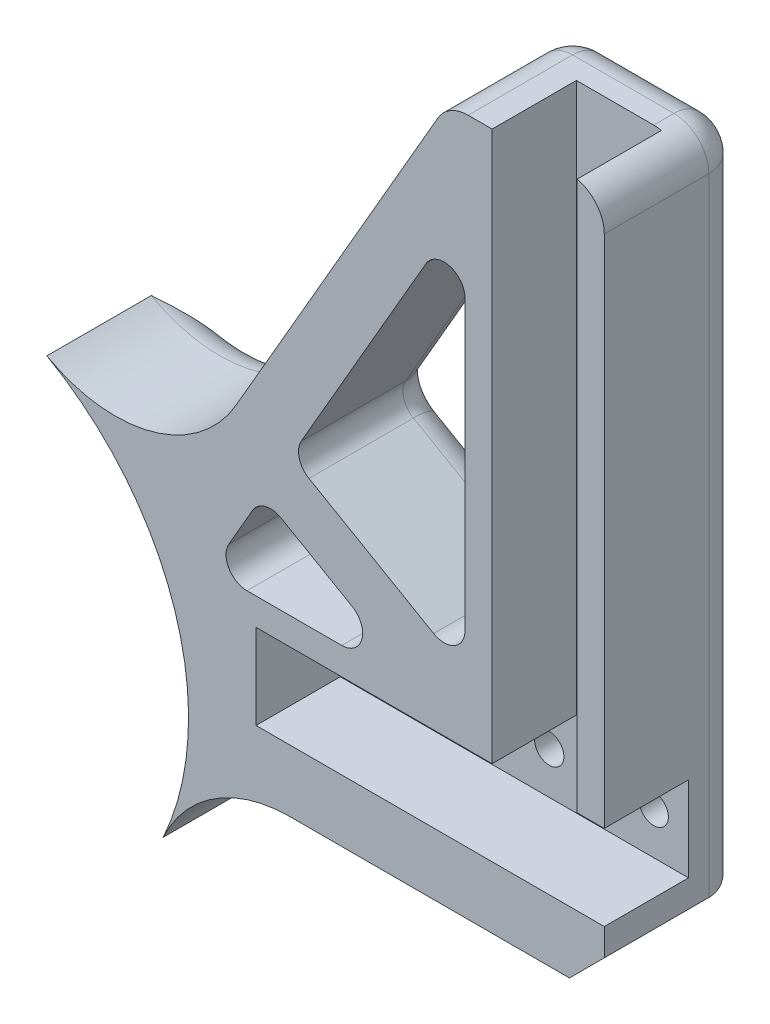
SolidWorks part; units mm, degrees
material "ABS"
ref_plane "前视基准面" through (0, 0, 0) normal (0, 0, 1) x (1, 0, 0)
ref_plane "上视基准面" through (0, 0, 0) normal (0, 1, 0) x (1, 0, 0)
ref_plane "右视基准面" through (0, 0, 0) normal (1, 0, 0) x (0, 0, -1)
other "Configuration Table"
sketch "草图1" plane through (0, 0, 0) normal (0, 0, 1) x (1, 0, 0)
  circle A0 centre (0, 0) radius 40
  circle A10 centre (0, 0) radius 32.5
  dimension "D1" = 80
  dimension "D6" = 65
extrude "凸台-拉伸1" add sketch "草图1" along normal blind 20
sketch "草图2" plane through (0, 0, 20) normal (0, 0, 1) x (1, 0, 0)
  line L0 (0, 0) -> (40, 0) construction
  line L1 (0, 0) -> (36.5, 0) construction
  circle A0 centre (0, 0) radius 40 construction
  point P6 (36.5, 0)
  point P7 (27.9606, -23.4617)
  point P10 (6.3382, -35.9455)
  point P11 (-18.25, -31.6099)
  point P12 (-34.2988, -12.4837)
  point P13 (-34.2988, 12.4837)
  point P14 (-18.25, 31.6099)
  point P15 (6.3382, 35.9455)
  point P16 (27.9606, 23.4617)
  dimension "D3" = 36.5
  dimension "D2" = 9
hole_wizard "M3 六角凹锥坑螺钉的锥形沉头孔1" [suppressed] positions "草图2" profile "草图3" countersink size "M3" standard "ISO"
sketch "草图3" plane through (27.9606, 23.4617, 4) normal (1, 0, 0) x (0, -1, 0)
  line L0 (0, 0) -> (0, 4)
  line L1 (0, 4) -> (1.7, 4)
  line L2 (1.7, 4) -> (1.7, 1.66)
  line L3 (1.7, 1.66) -> (3.36, 0)
  line L5 (3.36, 0) -> (0, 0)
  line L6 (-1.7, 1.66) -> (-3.36, 0) construction
  line L11 (0, -6.35) -> (0, 107.95) construction
  dimension "通孔孔直径" = 3.4
  dimension "通孔孔深度" = 4
  dimension "近端锥形沉头孔直径" = 6.72
  dimension "近端锥形沉头孔角度" = 90
sketch "草图4" plane through (0, 0, 20) normal (0, 0, 1) x (1, 0, 0)
  line L0 (0, 0) -> (40, 0) construction
  line L11 (39.6863, -5) -> (99.6863, -5)
  line L23 (77.2499, 95) -> (99.6863, 95)
  line L26 (99.6863, 95) -> (99.6863, -5)
  line L27 (77.2499, 95) -> (34.2914, 20.5937)
  line L28 (79.6863, 83.2199) -> (43.1863, 20) construction
  line L29 (43.1863, 20) -> (79.6863, 20) construction
  line L30 (79.6863, 20) -> (79.6863, 83.2199) construction
  line L32 (54.6863, 39.9186) -> (79.6863, 25.4848)
  line L33 (50.6863, 32.9904) -> (73.1863, 20)
  line L34 (79.6863, 83.2199) -> (54.6863, 39.9186)
  line L35 (79.6863, 83.2199) -> (79.6863, 25.4848)
  line L36 (50.6863, 32.9904) -> (43.1863, 20)
  line L37 (43.1863, 20) -> (73.1863, 20)
  line L38 (89.6863, 95) -> (89.6863, -5) construction
  circle A0 centre (0, 0) radius 40 construction
  circle A5 centre (79.6863, 10) radius 1.55
  circle A13 centre (94.6863, 10) radius 1.55
  circle A29 centre (64.6863, 10) radius 1.55
  circle A34 centre (89.6863, 76) radius 1.55
  arc A42 (34.2914, 20.5937) -> (39.6863, -5) centre (0, 0) cw
  circle A43 centre (89.6863, 61) radius 1.55
  circle A44 centre (89.6863, 46) radius 1.55
  circle A45 centre (89.6863, 31) radius 1.55
  dimension "D1" = 5
  dimension "D2" = 20
  dimension "D8" = 3.1
  dimension "D9" = 3.1
  dimension "D10" = 15
  dimension "D15" = 15
  dimension "D16" = 15
  dimension "D18" = 10
  dimension "D19" = 3.1
  dimension "D25" = 15
  dimension "D26" = 50
  dimension "D27" = 3.1
  dimension "D6" = 60
  dimension "D11" = 15
  dimension "D3" = 60
  dimension "D14" = 3.1
  dimension "D20" = 3.1
  dimension "D21" = 3.1
  dimension "D4" = 100
  dimension "D5" = 25
  dimension "D7" = 8
  dimension "D12" = 15
  dimension "D13" = 5
  dimension "D17" = 8
  dimension "D22" = 19
  dimension "D23" = 15
  dimension "D24" = 15
  dimension "D28" = 15
extrude "凸台-拉伸2" add sketch "草图4" against normal up to surface (20 mm away) up to face at (40, 0, 0)
fillet "圆角1" [suppressed] radius 10
fillet "圆角2" radius 20 2 edges at (39.6863, -5, 10) (34.2914, 20.5937, 10)
fillet "圆角3" [suppressed] radius 20
chamfer "倒角1" distance 5 angle 45 1 edges at (99.6863, -5, 10)
fillet "圆角4" radius 3 6 edges at (43.1863, 20, 10) (50.6863, 32.9904, 10) (73.1863, 20, 10) (54.6863, 39.9186, 10) (79.6863, 83.2199, 10) (79.6863, 25.4848, 10)
fillet "圆角5" radius 5 2 edges at (77.2499, 95, 10) (99.6863, 95, 10)
sketch "草图6" plane through (0, 0, 20) normal (0, 0, 1) x (1, 0, 0)
  circle A0 centre (0, 0) radius 40
  dimension "D1" = 80
extrude "切除-拉伸1" cut sketch "草图6" against normal through all
sketch "草图7" plane through (0, 0, 20) normal (0, 0, 1) x (1, 0, 0)
  line L0 (99.6863, 0) -> (99.6863, 90) construction
  line L1 (49.6863, 16.1) -> (83.5863, 16.1)
  line L2 (49.6863, 16.1) -> (49.6863, 3.9)
  line L3 (49.6863, 3.9) -> (99.6863, 3.9)
  line L4 (99.6863, 16.1) -> (99.6863, 3.9)
  line L5 (94.6863, 95) -> (80.1367, 95) construction
  line L6 (83.5863, 95) -> (95.7863, 95)
  line L7 (83.5863, 95) -> (83.5863, 16.1)
  line L9 (95.7863, 95) -> (95.7863, 16.1)
  line L11 (89.6863, 76) -> (89.6863, 31) construction
  line L12 (64.6863, 10) -> (94.6863, 10) construction
  line L13 (95.7863, 16.1) -> (99.6863, 16.1)
  dimension "D1" = 6.1
  dimension "D3" = 50
  dimension "D4" = 6.1
  dimension "D5" = 6.1
  dimension "D6" = 6.1
extrude "切除-拉伸2" cut sketch "草图7" against normal blind 12.1
sketch "草图8" plane through (0, 0, 7.9) normal (0, 0, 1) x (1, 0, 0)
  circle A0 centre (94.6863, 10) radius 2.1
  circle A1 centre (89.6863, 31) radius 2.1
  circle A2 centre (79.6863, 10) radius 2.1
  circle A3 centre (64.6863, 10) radius 2.1
  circle A4 centre (89.6863, 46) radius 2.05
  circle A5 centre (89.6863, 61) radius 2.05
  circle A6 centre (89.6863, 76) radius 2.05
  dimension "D1" = 4.1
  dimension "D2" = 4.1
  dimension "D3" = 4.1
  dimension "D4" = 4.2
  dimension "D5" = 4.2
  dimension "D6" = 4.2
  dimension "D7" = 4.2
extrude "切除-拉伸3" cut sketch "草图8" against normal blind 4.5
sketch "草图9" plane through (0, 0, 0) normal (0, 0, -1) x (-1, 0, 0)
  circle A0 centre (-89.6863, 76) radius 1.55
  circle A1 centre (-89.6863, 61) radius 1.55
  circle A2 centre (-89.6863, 46) radius 1.55
  circle A3 centre (-89.6863, 31) radius 1.55
  circle A4 centre (-79.6863, 10) radius 1.55
  circle A5 centre (-64.6863, 10) radius 1.55
  circle A6 centre (-94.6863, 10) radius 1.55
extrude "凸台-拉伸3" add sketch "草图9" against normal up to surface (3.4 mm away) up to face at (91.7363, 76, 3.4)
fillet "圆角6" radius 5 21 edges at (51.0079, 31.7901, 0) (47.4853, 27.4462, 0) (45.7843, 21.5, 0) (55.1863, 20, 0) (64.8879, 22.2235, 0) (55.8866, 40.2402, 0) (66.2353, 33.2507, 0) (78.1863, 28.0829, 0) (79.6863, 51.3523, 0) (77.4627, 74.9215, 0) (43.7423, -8.1675, 0) (34.7521, 32.9663, 0) (61.3032, 67.3794, 0) (77.6367, 94.3301, 0) (87.4115, 95, 0) (98.2218, 93.5355, 0) (58.3872, 28.5442, 0) (65.1372, 58.0202, 0) (97.1863, -2.5, 0) (74.6149, -5, 0) (99.6863, 45, 0)
